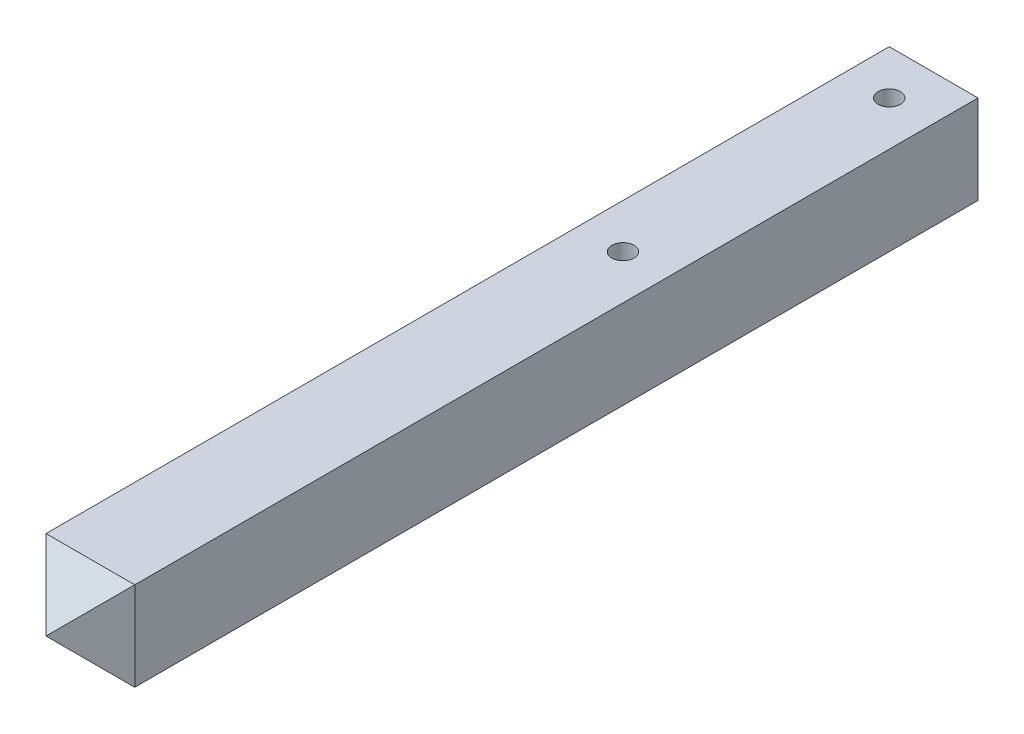
SolidWorks part; units mm, degrees
ref_plane "Front Plane" through (0, 0, 0) normal (0, 0, 1) x (1, 0, 0)
ref_plane "Top Plane" through (0, 0, 0) normal (0, 1, 0) x (1, 0, 0)
ref_plane "Right Plane" through (0, 0, 0) normal (1, 0, 0) x (0, 0, -1)
sketch "Sketch1" plane through (0, 0, 0) normal (0, 1, 0) x (1, 0, 0)
  line L1 (0, 0) -> (20, 0)
  line L2 (0, 0) -> (0, -200)
  line L3 (0, -200) -> (20, -200)
  line L4 (20, 0) -> (20, -200)
  circle A0 centre (10, -10) radius 2.5
  circle A1 centre (10, -70) radius 2.5
  dimension "D3" = 5
  dimension "D4" = 5
  dimension "D5" = 60
  dimension "D6" = 10
  dimension "D1" = 20
  dimension "D2" = 200
extrude "Boss-Extrude1" add sketch "Sketch1" along normal blind 20
chamfer "Chamfer1" distance 10 angle 45 4 edges at (20, 10, 200) (10, 0, 200) (0, 10, 200) (10, 20, 200)
scale "Scale1" scale about centroid uniform scaling yes scale factor 7.5
